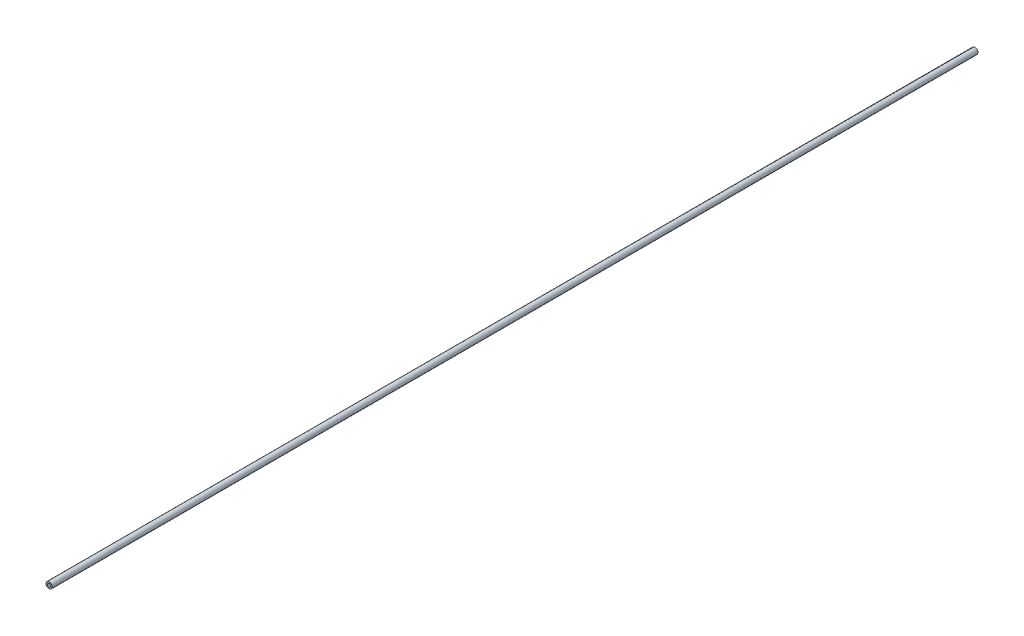
SolidWorks part; units mm, degrees
material "6061 Alloy"
ref_plane "Front Plane" through (0, 0, 0) normal (0, 0, 1) x (1, 0, 0)
ref_plane "Top Plane" through (0, 0, 0) normal (0, 1, 0) x (1, 0, 0)
ref_plane "Right Plane" through (0, 0, 0) normal (1, 0, 0) x (0, 0, -1)
sketch "Sketch1" plane through (0, 0, 0) normal (0, 0, 1) x (1, 0, 0)
  circle A0 centre (0, 0) radius 12.7
  circle A1 centre (0, 0) radius 6.35
  dimension "D1" = 25.4
  dimension "D2" = 12.7
extrude "Boss-Extrude4" add sketch "Sketch1" along normal blind 3850.2541
equation "\"Force\"= 350'lbf"
equation "\"Elastic_modulus\" = 10007603'psi"
equation "\"height\" = 1in'in."
equation "\"th\" = 0.25in'in."
equation "\"width\" = 1in'in."
equation "\"A\" = ( pi / 4 ) * ( \"do\" ^ 2 - \"di\" ^ 2 )'square in."
equation "\"L\"= ( \"delfection\" * \"A\" * \"Elastic_modulus\" ) / \"Force\""
equation "\"di\" = 0.5in"
equation "\"do\" = 1in"
equation "\"delfection\" = 0.009in"
equation "\"D1@Sketch1\"= \"do\""
equation "\"D2@Sketch1\"=\"di\""
equation "\"D1@Boss-Extrude4\"=\"L\""
